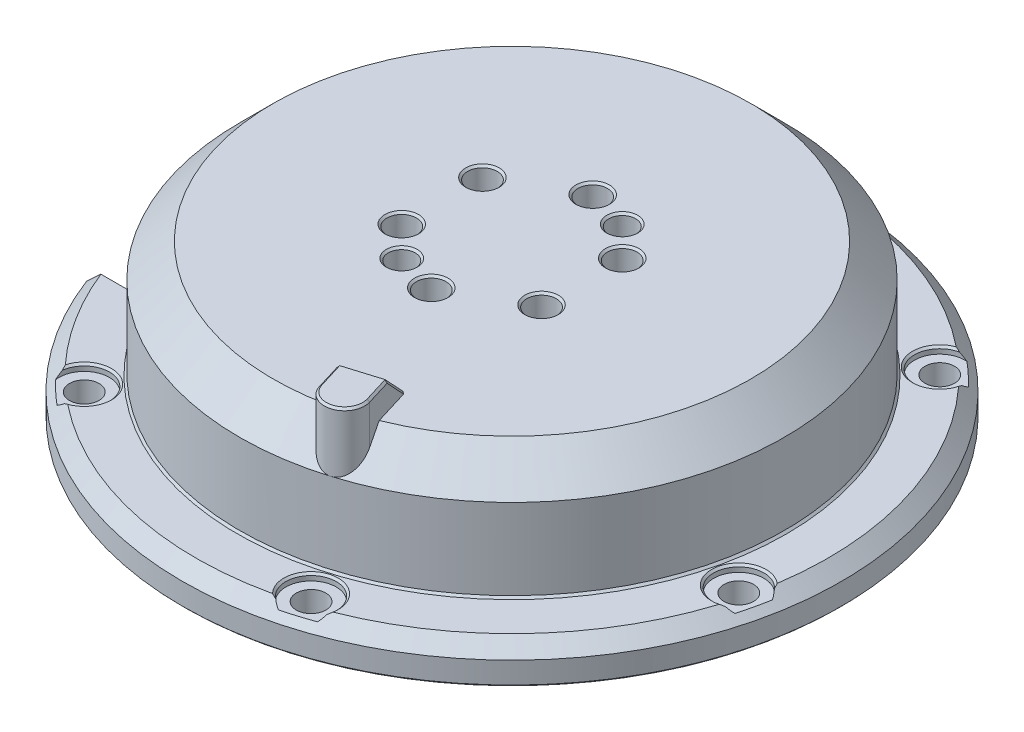
SolidWorks part; units mm, degrees
material "6061-T6 (SS)"
ref_plane "정면" through (0, 0, 0) normal (0, 0, 1) x (1, 0, 0)
ref_plane "윗면" through (0, 0, 0) normal (0, 1, 0) x (1, 0, 0)
ref_plane "우측면" through (0, 0, 0) normal (1, 0, 0) x (0, 0, -1)
sketch "스케치1" plane through (0, 0, 0) normal (0, 1, 0) x (1, 0, 0)
  circle A0 centre (0, 0) radius 49
  circle A1 centre (0, 0) radius 40.5
  circle A2 centre (0, 0) radius 36.5
  dimension "D1" = 98
  dimension "D2" = 81
  dimension "D3" = 73
extrude "보스-돌출1" add sketch "스케치1" along normal blind 5.5 contours A0 A1 region at (-47.6141, 0, 0)
extrude "보스-돌출2" add sketch "스케치1<5>" along normal blind 17.8 contours A1 A2 region at (-39.3545, 0, 0)
sketch "스케치1<5>" plane through (0, 0, 0) normal (0, 1, 0) x (1, 0, 0) same geometry as "스케치1"
extrude "보스-돌출3" add sketch "스케치1<6>" along normal blind 5 from surface contours A2 | A1 A2 region at (-39.3545, 0, 0) region at (0, 0, 0) starting at face at (0, 17.8, 36.5)
sketch "스케치1<6>" plane through (0, 0, 0) normal (0, 1, 0) x (1, 0, 0) same geometry as "스케치1"
sketch "스케치2" plane through (0, 22.8, 0) normal (0, 1, 0) x (1, 0, 0)
  line L0 (6, 10.3923) -> (-6, -10.3923) construction
  line L1 (0, 12) -> (0, 0) construction
  circle A0 centre (0, 0) radius 12
  circle A1 centre (0, 12) radius 2.2
  circle A2 centre (10.3923, 6) radius 2.2
  circle A3 centre (10.3923, -6) radius 2.2
  circle A4 centre (0, -12) radius 2.2
  circle A5 centre (-10.3923, -6) radius 2.2
  circle A6 centre (-10.3923, 6) radius 2.2
  circle A7 centre (6, 10.3923) radius 2
  circle A8 centre (-6, -10.3923) radius 2
  point P17 (0, 0)
  point P20 (0, 0)
  dimension "D1" = 24
  dimension "D2" = 4.4
  dimension "D4" = 4
  dimension "D5" = 30
  dimension "D3" = 6
extrude "컷-돌출1" cut sketch "스케치2" against normal blind 50 contours A0 A6 | A0 A6 | A0 A5 | A0 A5 | A0 A1 | A0 A1 | A0 A2 | A0 A2 | A0 A3 | A0 A3 | A0 A4 | A0 A4 region at (9.5531, 22.8, -5.5155) region at (11.1687, 22.8, -6.4482) region at (11.1687, 22.8, 6.4482) region at (9.5531, 22.8, 5.5155) region at (0, 22.8, 12.8964) region at (0, 22.8, 11.0309) region at (0, 22.8, -11.0309) region at (0, 22.8, -12.8964) region at (-9.5531, 22.8, -5.5155) region at (-11.1687, 22.8, -6.4482) region at (-11.1687, 22.8, 6.4482) region at (-9.5531, 22.8, 5.5155)
sketch "스케치3" plane through (0, 5.5, 0) normal (0, 1, 0) x (1, 0, 0)
  line L0 (-43.8467, 10.1228) -> (0, 0) construction
  line L1 (0, 0) -> (-45, 0) construction
  circle A0 centre (0, 0) radius 45
  circle A1 centre (-43.8467, 10.1228) radius 2.2
  circle A2 centre (-13.1567, 43.0337) radius 2.2
  circle A3 centre (30.6899, 32.9109) radius 2.2
  circle A4 centre (43.8467, -10.1228) radius 2.2
  circle A5 centre (13.1567, -43.0337) radius 2.2
  circle A6 centre (-30.6899, -32.9109) radius 2.2
  point P18 (0, 0)
  dimension "D1" = 90
  dimension "D2" = 4.4
  dimension "D3" = 13
  dimension "D4" = 6
extrude "컷-돌출2" cut sketch "스케치3" against normal blind 50 contours A0 A1 | A0 A1 | A0 A2 | A0 A2 | A0 A3 | A0 A3 | A0 A4 | A0 A4 | A0 A5 | A0 A5 | A0 A6 | A0 A6 region at (30.0466, 5.5, -32.221) region at (31.3201, 5.5, -33.5867) region at (44.7469, 5.5, 10.3306) region at (42.9275, 5.5, 9.9106) region at (-12.8809, 5.5, -42.1316) region at (-13.4269, 5.5, -43.9173) region at (13.4269, 5.5, 43.9173) region at (12.8809, 5.5, 42.1316) region at (-42.9275, 5.5, -9.9106) region at (-44.7469, 5.5, -10.3306) region at (-31.3201, 5.5, 33.5867) region at (-30.0466, 5.5, 32.221)
sketch "스케치4" plane through (0, 0, 0) normal (0, -1, 0) x (1, 0, 0)
  line L1 (-65.9688, 17.5) -> (-32.0312, 17.5)
  line L2 (-65.9688, 17.5) -> (-65.9688, -17.5)
  line L3 (-65.9688, -17.5) -> (-32.0312, -17.5)
  line L4 (-32.0312, 17.5) -> (-32.0312, -17.5)
  line L5 (-65.9688, 17.5) -> (-32.0312, -17.5) construction
  line L6 (-65.9688, -17.5) -> (-32.0312, 17.5) construction
  circle A0 centre (0, 0) radius 49 construction
  circle A1 centre (0, 0) radius 36.5 construction
  point P0 (-49, 0)
  dimension "D1" = 35
extrude "컷-돌출3" cut sketch "스케치4" against normal blind 11
sketch "스케치5" plane through (0, 22.8, 0) normal (0, 1, 0) x (1, 0, 0)
  line L0 (-9.9248, 17.1902) -> (0, 0) construction
  line L1 (0, 0) -> (9.9248, 17.1902) construction
  line L2 (-44.2742, 6.1457) -> (-19.4755, 3.48)
  line L3 (-16.8147, 41.4154) -> (-6.724, 18.6063)
  line L4 (-9.6674, 44.9893) -> (6.8716, 15.4791)
  line L5 (12.7515, 15.1263) -> (27.4594, 35.2697)
  line L6 (16.8411, 1.7886) -> (34.1282, 30.8668)
  line L7 (19.4755, -3.48) -> (44.2742, -6.1457)
  line L8 (9.9695, -13.6905) -> (43.7956, -14.1225)
  line L9 (6.724, -18.6063) -> (16.8147, -41.4154)
  line L10 (-6.8716, -15.4791) -> (9.6674, -44.9893)
  line L11 (-12.7515, -15.1263) -> (-27.4594, -35.2697)
  line L12 (-16.8411, -1.7886) -> (-34.1282, -30.8668)
  line L13 (-43.7956, 14.1225) -> (-9.9695, 13.6905)
  line L14 (-13.1567, 43.0337) -> (0, 0) construction
  line L15 (0, 0) -> (30.6899, 32.9109) construction
  circle A0 centre (0, 0) radius 8
  circle A1 centre (-9.9248, 17.1902) radius 9
  circle A2 centre (9.9248, 17.1902) radius 9
  circle A3 centre (19.8496, 0) radius 9
  circle A4 centre (9.9248, -17.1902) radius 9
  circle A5 centre (-9.9248, -17.1902) radius 9
  circle A6 centre (-19.8496, 0) radius 9
  circle A7 centre (-10.3923, 6) radius 2.2 construction
  circle A8 centre (0, 12) radius 2.2 construction
  circle A9 centre (10.3923, 6) radius 2.2 construction
  circle A10 centre (-10.3923, -6) radius 2.2 construction
  circle A11 centre (0, -12) radius 2.2 construction
  circle A12 centre (10.3923, -6) radius 2.2 construction
  circle A13 centre (-9.9248, 17.1902) radius 3.5
  circle A14 centre (9.9248, 17.1902) radius 3.5
  circle A15 centre (19.8496, 0) radius 3.5
  circle A16 centre (9.9248, -17.1902) radius 3.5
  circle A17 centre (-9.9248, -17.1902) radius 3.5
  circle A18 centre (-19.8496, 0) radius 3.5
  circle A27 centre (-13.1567, 43.0337) radius 4
  circle A28 centre (30.6899, 32.9109) radius 4
  circle A29 centre (43.8467, -10.1228) radius 4
  circle A30 centre (13.1567, -43.0337) radius 4
  circle A31 centre (-30.6899, -32.9109) radius 4
  circle A32 centre (-43.8467, 10.1228) radius 4
  circle A33 centre (0, 0) radius 49
  point P41 (0, 0)
  point P91 (0, 0)
  dimension "D1" = 16
  dimension "D2" = 18
  dimension "D5" = 7
  dimension "D8" = 8
  dimension "D4" = 60
  dimension "D9" = 60
  dimension "D3" = 6
  dimension "D7" = 6
sketch "스케치7" plane through (0, 5.5, 0) normal (0, 1, 0) x (1, 0, 0)
  line L0 (-13.1567, 43.0337) -> (0, 0) construction
  line L1 (0, 0) -> (30.6899, 32.9109) construction
  circle A0 centre (-13.1567, 43.0337) radius 3.75
  circle A1 centre (30.6899, 32.9109) radius 3.75
  circle A2 centre (43.8467, -10.1228) radius 3.75
  circle A3 centre (13.1567, -43.0337) radius 3.75
  circle A4 centre (-30.6899, -32.9109) radius 3.75
  circle A5 centre (-43.8467, 10.1228) radius 3.75
  point P15 (0, 0)
  dimension "D1" = 7.5
  dimension "D3" = 60
  dimension "D2" = 6
extrude "컷-돌출5" cut sketch "스케치7" against normal blind 1
chamfer "모따기8" distance 0.3 angle 45 7 edges at (0, 17.8, 36.5) (36.5, 0, 0) (49, 0, 0) (-34.2776, 11, 17.5) (-34.2776, 11, -17.5) (-38.8998, 0, 17.5) (-38.8998, 0, -17.5)
chamfer "모따기9" distance 2 angle 45 1 edges at (49, 5.5, 0)
sketch "스케치8" plane through (0, 22.8, 0) normal (0, 1, 0) x (1, 0, 0)
  line L0 (0, 0) -> (10.9639, -35.8614) construction
  line L1 (0, 0) -> (0, -40.5) construction
  line L2 (5.7561, -29.0881) -> (8.095, -36.7385)
  line L3 (11.4939, -27.3339) -> (13.8329, -34.9843)
  line L4 (5.7561, -29.0881) -> (11.4939, -27.3339)
  line L5 (8.095, -36.7385) -> (13.8329, -34.9843) construction
  circle A0 centre (10.9639, -35.8614) radius 3
  arc A3 (-36.524, -17.5) -> (-36.524, 17.5) centre (0, 0) ccw construction
  dimension "D3" = 6
  dimension "D1" = 8
  dimension "D2" = 17
fillet "필렛1" [suppressed] radius 5
sketch "스케치9" plane through (0, 5.5, 0) normal (0, 1, 0) x (1, 0, 0)
  line L0 (0, 0) -> (-15.8246, -37.2804)
  line L1 (0, 0) -> (-2.1196, -40.4445)
  line L2 (24.3735, -32.3447) -> (0, 0)
  line L3 (0, 0) -> (33.9662, -22.0579)
  line L4 (40.1981, 4.9357) -> (0, 0)
  line L5 (0, 0) -> (36.0858, 18.3866)
  line L6 (15.8246, 37.2804) -> (0, 0)
  line L7 (2.1196, 40.4445) -> (0, 0)
  line L8 (-24.3735, 32.3447) -> (0, 0)
  line L9 (-33.9662, 22.0579) -> (0, 0)
  line L10 (-30.6899, -32.9109) -> (0, 0) construction
  line L11 (0, 0) -> (13.1567, -43.0337) construction
  line L12 (0, 0) -> (43.8467, -10.1228) construction
  line L13 (30.6899, 32.9109) -> (0, 0) construction
  line L14 (-13.1567, 43.0337) -> (0, 0) construction
  circle A0 centre (0, 0) radius 40.5
  arc M22 (-36.524, 17.5) -> (-36.524, -17.5) centre (0, 0) cw
  dimension "D1" = 81
  dimension "D2" = 20
  dimension "D3" = 20
  dimension "D4" = 20
  dimension "D5" = 20
  dimension "D6" = 20
  dimension "D7" = 20
extrude "컷-돌출7" [suppressed] cut sketch "스케치9" along normal up to surface (12.5 mm away) contours L1 L0 M22 | L3 L2 M22 | L5 L4 M22 | L7 L6 M22 | L9 L8 M22 up to face at (0, 17.8, 36.2)
chamfer "모따기11" distance 0.3 angle 45 1 edges at (40.5, 5.5, 0)
extrude "보스-돌출4" add sketch "스케치8" along normal blind 4 contours A0 | A0 L3 L4 L2 region at (9.4616, 22.8, 30.9476) region at (10.9639, 22.8, 35.8614)
chamfer "모따기12" distance 5 angle 45 1 edges at (0, 22.8, 40.5)
sketch "스케치10" plane through (-2.8689, 0, 0.8771) normal (-0.9563, 0, 0.2924) x (0.2924, 0, 0.9563)
  line L0 (29.5, 22.8) -> (33.5, 26.8)
  line L1 (29.5, 26.8) -> (37.5, 26.8) construction
  line L2 (33.5, 26.8) -> (29.5, 26.8)
  line L3 (29.5, 26.8) -> (29.5, 22.8)
extrude "컷-돌출8" cut sketch "스케치10" against normal blind 10
chamfer "모따기13" distance 0.3 angle 45 5 edges at (6.3408, 24.8, 31.0007) (12.0786, 24.8, 29.2465) (7.5103, 26.8, 34.8259) (11.8411, 26.8, 38.7303) (13.2481, 26.8, 33.0717)
extrude "컷-돌출9" cut sketch "스케치2<3>" against normal blind 4.5 contours A0 A7 | A0 A7 | A0 A8 | A0 A8 region at (5.5609, 22.8, -9.6318) region at (6.4091, 22.8, -11.1008) region at (-6.4091, 22.8, 11.1008) region at (-5.5609, 22.8, 9.6318)
sketch "스케치2<3>" plane through (0, 22.8, 0) normal (0, 1, 0) x (1, 0, 0) same geometry as "스케치2"
chamfer "모따기10" distance 0.3 angle 45 19 edges at (28.1324, 5.5, -30.1683) (40.1928, 5.5, 9.2792) (12.0603, 5.5, 39.4476) (-28.1324, 5.5, 30.1683) (-12.0603, 5.5, -39.4476) (0, 17.8, -9.8) (-10.3923, 17.8, -3.8) (-10.3923, 17.8, 8.2) (0, 17.8, 14.2) (10.3923, 17.8, -3.8) (10.3923, 17.8, 8.2) (0, 22.8, -9.8) (-10.3923, 22.8, -3.8) (-10.3923, 22.8, 8.2) (-6, 22.8, 12.3923) (0, 22.8, 14.2) (10.3923, 22.8, 8.2) (6, 22.8, -8.3923) (10.3923, 22.8, -3.8)
